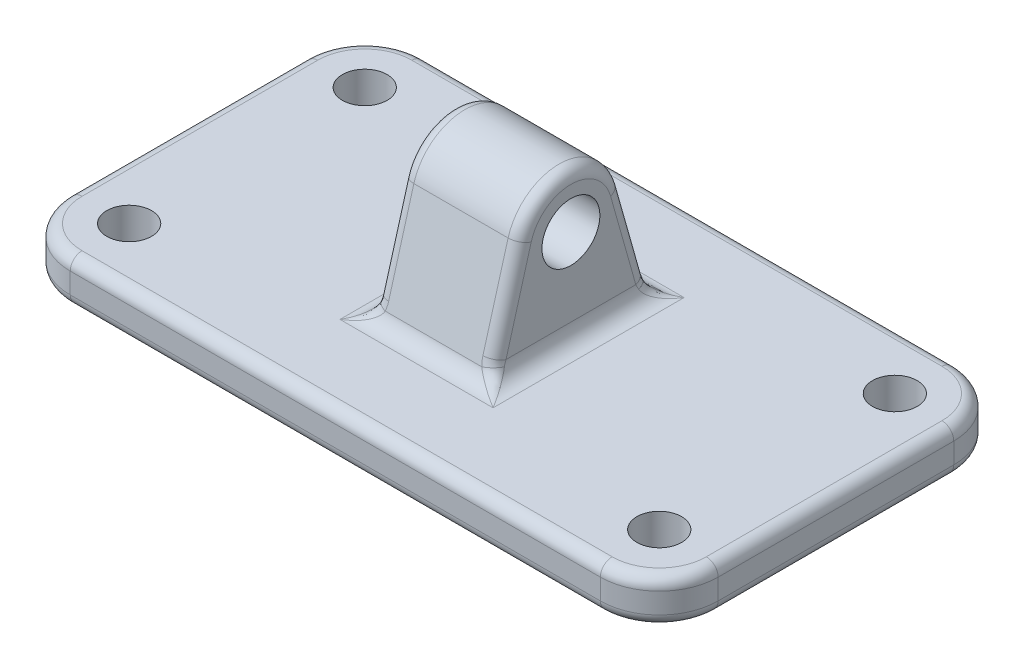
SolidWorks part; units mm, degrees
ref_plane "Ön Düzlem" through (0, 0, 0) normal (0, 0, 1) x (1, 0, 0)
ref_plane "Üst Düzlem" through (0, 0, 0) normal (0, 1, 0) x (1, 0, 0)
ref_plane "Sağ Düzlem" through (0, 0, 0) normal (1, 0, 0) x (0, 0, -1)
sketch "Çizim1" plane through (0, 0, 0) normal (0, 1, 0) x (1, 0, 0)
  line L0 (-57.15, 25.4) -> (57.15, 25.4) construction
  line L1 (-69.85, 38.1) -> (69.85, 38.1)
  line L2 (-69.85, 38.1) -> (-69.85, -38.1)
  line L3 (-69.85, -38.1) -> (69.85, -38.1)
  line L4 (69.85, 38.1) -> (69.85, -38.1)
  line L5 (-69.85, 38.1) -> (69.85, -38.1) construction
  line L6 (-69.85, -38.1) -> (69.85, 38.1) construction
  line L7 (57.15, 25.4) -> (57.15, -25.4) construction
  line L8 (-57.15, -25.4) -> (57.15, -25.4) construction
  line L9 (-57.15, 25.4) -> (-57.15, -25.4) construction
  circle A0 centre (-57.15, 25.4) radius 4.826
  circle A1 centre (-57.15, -25.4) radius 4.826
  circle A2 centre (57.15, -25.4) radius 4.826
  circle A3 centre (57.15, 25.4) radius 4.826
  point P0 (0, 0)
  dimension "D4" = 9.652
  dimension "D1" = 76.2
  dimension "D2" = 139.7
  dimension "D3" = 12.7
extrude "Yükseklik-Ekstrüzyon1" add sketch "Çizim1" along normal mid plane 9.525
sketch "Çizim2" plane through (0, 0, 0) normal (1, 0, 0) x (0, 0, -1)
  line L0 (-19.05, 0) -> (19.05, 0)
  line L1 (0, 0) -> (0, 25.4) construction
  line L2 (-19.05, 0) -> (-10.9998, 28.5063)
  line L3 (19.05, 0) -> (10.9998, 28.5063)
  circle A0 centre (0, 25.4) radius 6.25
  arc A1 (10.9998, 28.5063) -> (-10.9998, 28.5063) centre (0, 25.4) ccw
  point P3 (0, 0)
  dimension "D3" = 12.5
  dimension "D4" = 22.86
  dimension "D1" = 38.1
  dimension "D2" = 25.4
extrude "Yükseklik-Ekstrüzyon2" add sketch "Çizim2" along normal mid plane 25.4
fillet "Radyus1" radius 12.7 4 edges at (69.85, 0, 38.1) (-69.85, 0, 38.1) (-69.85, 0, -38.1) (69.85, 0, -38.1)
fillet "Radyus2" radius 2.54 16 edges at (66.1303, -4.7625, -34.3803) (69.85, -4.7625, 0) (66.1303, -4.7625, 34.3803) (0, -4.7625, 38.1) (-66.1303, -4.7625, 34.3803) (-69.85, -4.7625, 0) (-66.1303, -4.7625, -34.3803) (66.1303, 4.7625, -34.3803) (69.85, 4.7625, 0) (66.1303, 4.7625, 34.3803) (0, 4.7625, 38.1) (-66.1303, 4.7625, 34.3803) (-69.85, 4.7625, 0) (-66.1303, 4.7625, -34.3803) (0, -4.7625, -38.1) (0, 4.7625, -38.1)
fillet "Radyus3" radius 3.81 4 edges at (0, 4.7625, 17.7051) (-12.7, 4.7625, 0) (0, 4.7625, -17.7051) (12.7, 4.7625, 0)
fillet "Radyus4" radius 2.54 14 edges at (-14.211, 5.5343, -18.2891) (-12.736, 8.0498, -16.7767) (-14.211, 5.5343, 18.2891) (-12.736, 8.0498, 16.7767) (-12.7, 18.5394, 13.8145) (-12.7, 36.83, 0) (14.211, 5.5343, -18.2891) (12.736, 8.0498, -16.7767) (14.211, 5.5343, 18.2891) (12.736, 8.0498, 16.7767) (12.7, 18.5394, 13.8145) (12.7, 36.83, 0) (-12.7, 18.5394, -13.8145) (12.7, 18.5394, -13.8145)
